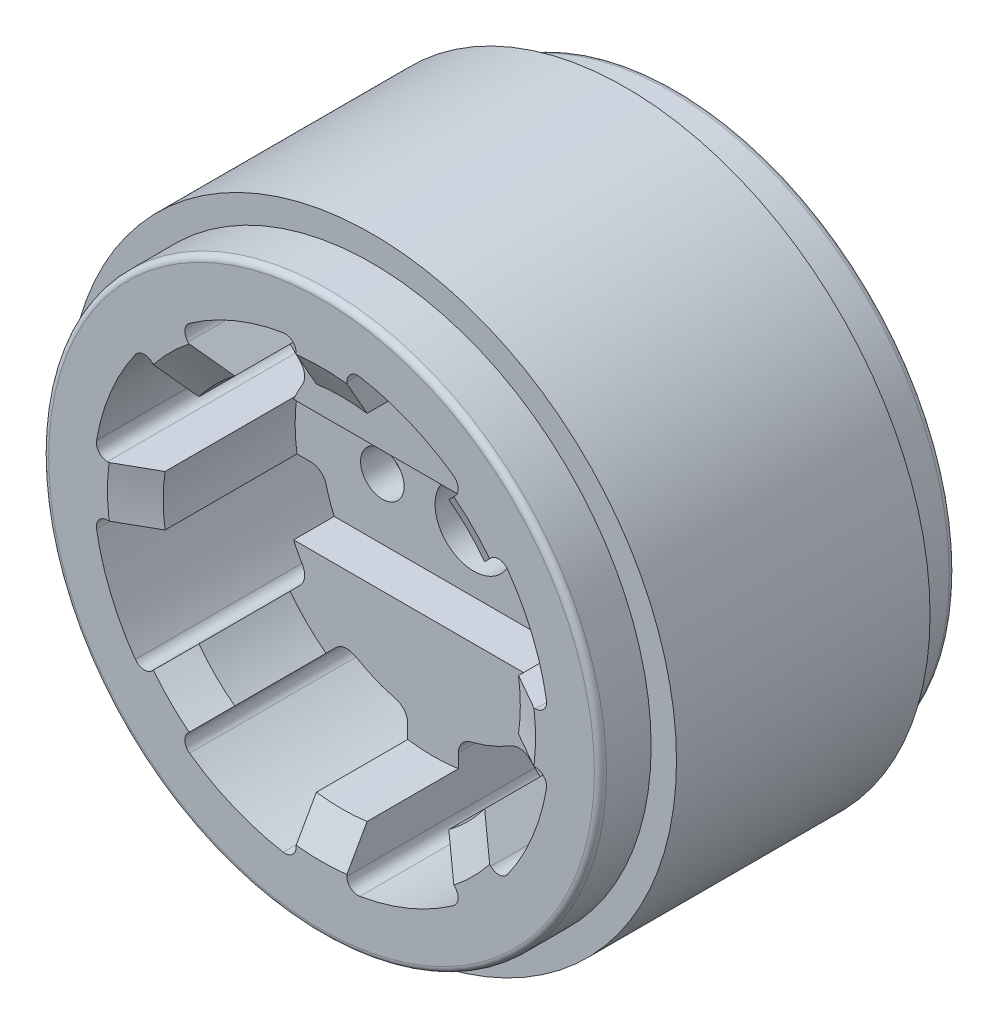
SolidWorks part; units mm, degrees
ref_plane "Front Plane" through (0, 0, 0) normal (0, 0, 1) x (1, 0, 0)
ref_plane "Top Plane" through (0, 0, 0) normal (0, 1, 0) x (1, 0, 0)
ref_plane "Right Plane" through (0, 0, 0) normal (1, 0, 0) x (0, 0, -1)
sketch "Sketch1" plane through (0, 0, 0) normal (0, 0, 1) x (1, 0, 0)
  line L0 (0, 0) -> (52.3745, 0) construction
  line L1 (0, 0) -> (0, 45.9782) construction
  line L2 (2.5, 21.1024) -> (2.5, 16.0565)
  line L3 (-13.7477, 6) -> (13.7477, 6)
  line L4 (-13.7477, -6) -> (13.7477, -6)
  line L5 (-2.5, 21.1024) -> (-2.5, 16.0565)
  line L6 (16.6894, 13.1539) -> (13.1215, 9.5859)
  line L7 (13.1539, 16.6894) -> (9.5859, 13.1215)
  line L8 (21.1024, -2.5) -> (16.0565, -2.5)
  line L9 (21.1024, 2.5) -> (16.0565, 2.5)
  line L10 (13.1539, -16.6894) -> (9.5859, -13.1215)
  line L11 (16.6894, -13.1539) -> (13.1215, -9.5859)
  line L12 (-2.5, -21.1024) -> (-2.5, -16.0565)
  line L13 (2.5, -21.1024) -> (2.5, -16.0565)
  line L14 (-16.6894, -13.1539) -> (-13.1215, -9.5859)
  line L15 (-13.1539, -16.6894) -> (-9.5859, -13.1215)
  line L16 (-21.1024, 2.5) -> (-16.0565, 2.5)
  line L17 (-21.1024, -2.5) -> (-16.0565, -2.5)
  line L18 (-13.1539, 16.6894) -> (-9.5859, 13.1215)
  line L19 (-16.6894, 13.1539) -> (-13.1215, 9.5859)
  circle A0 centre (0, 0) radius 3.8
  circle A1 centre (0, 0) radius 15
  circle A2 centre (0, 0) radius 22.5
  circle A3 centre (0, 0) radius 27.5
  circle A4 centre (9, 0) radius 3
  circle A5 centre (-9, 0) radius 3
  arc A6 (2.5, 21.1024) -> (3.7774, 22.1807) centre (3.5937, 21.1024) cw
  circle A7 centre (9, 0) radius 2.15
  circle A8 centre (-9, 0) radius 2.15
  arc A9 (-2.5, 21.1024) -> (-3.7774, 22.1807) centre (-3.5937, 21.1024) ccw
  arc A10 (16.6894, 13.1539) -> (18.3551, 13.0131) centre (17.4628, 12.3805) cw
  arc A11 (13.1539, 16.6894) -> (13.0131, 18.3551) centre (12.3805, 17.4628) ccw
  arc A12 (21.1024, -2.5) -> (22.1807, -3.7774) centre (21.1024, -3.5937) cw
  arc A13 (21.1024, 2.5) -> (22.1807, 3.7774) centre (21.1024, 3.5937) ccw
  arc A14 (13.1539, -16.6894) -> (13.0131, -18.3551) centre (12.3805, -17.4628) cw
  arc A15 (16.6894, -13.1539) -> (18.3551, -13.0131) centre (17.4628, -12.3805) ccw
  arc A16 (-2.5, -21.1024) -> (-3.7774, -22.1807) centre (-3.5937, -21.1024) cw
  arc A17 (2.5, -21.1024) -> (3.7774, -22.1807) centre (3.5937, -21.1024) ccw
  arc A18 (-16.6894, -13.1539) -> (-18.3551, -13.0131) centre (-17.4628, -12.3805) cw
  arc A19 (-13.1539, -16.6894) -> (-13.0131, -18.3551) centre (-12.3805, -17.4628) ccw
  arc A20 (-21.1024, 2.5) -> (-22.1807, 3.7774) centre (-21.1024, 3.5937) cw
  arc A21 (-21.1024, -2.5) -> (-22.1807, -3.7774) centre (-21.1024, -3.5937) ccw
  arc A22 (-13.1539, 16.6894) -> (-13.0131, 18.3551) centre (-12.3805, 17.4628) cw
  arc A23 (-16.6894, 13.1539) -> (-18.3551, 13.0131) centre (-17.4628, 12.3805) ccw
  circle A24 centre (0, 0) radius 30
  circle A25 centre (0, 0) radius 17.6
  circle A26 centre (0, 0) radius 21.25
  circle A27 centre (0, 0) radius 16.25
  arc A28 (2.5, 16.0565) -> (3.6792, 14.5418) centre (4.0625, 16.0565) ccw
  arc A29 (-2.5, 16.0565) -> (-3.6792, 14.5418) centre (-4.0625, 16.0565) cw
  arc A30 (13.1215, 9.5859) -> (12.8842, 7.681) centre (14.2263, 8.4811) ccw
  arc A31 (9.5859, 13.1215) -> (7.681, 12.8842) centre (8.4811, 14.2263) cw
  arc A32 (16.0565, -2.5) -> (14.5418, -3.6792) centre (16.0565, -4.0625) ccw
  arc A33 (16.0565, 2.5) -> (14.5418, 3.6792) centre (16.0565, 4.0625) cw
  arc A34 (9.5859, -13.1215) -> (7.681, -12.8842) centre (8.4811, -14.2263) ccw
  arc A35 (13.1215, -9.5859) -> (12.8842, -7.681) centre (14.2263, -8.4811) cw
  arc A36 (-2.5, -16.0565) -> (-3.6792, -14.5418) centre (-4.0625, -16.0565) ccw
  arc A37 (2.5, -16.0565) -> (3.6792, -14.5418) centre (4.0625, -16.0565) cw
  arc A38 (-13.1215, -9.5859) -> (-12.8842, -7.681) centre (-14.2263, -8.4811) ccw
  arc A39 (-9.5859, -13.1215) -> (-7.681, -12.8842) centre (-8.4811, -14.2263) cw
  arc A40 (-16.0565, 2.5) -> (-14.5418, 3.6792) centre (-16.0565, 4.0625) ccw
  arc A41 (-16.0565, -2.5) -> (-14.5418, -3.6792) centre (-16.0565, -4.0625) cw
  arc A42 (-9.5859, 13.1215) -> (-7.681, 12.8842) centre (-8.4811, 14.2263) ccw
  arc A43 (-13.1215, 9.5859) -> (-12.8842, 7.681) centre (-14.2263, 8.4811) cw
  point P87 (0, 0)
  point P138 (0, 0)
  dimension "D1" = 7.6
  dimension "D2" = 30
  dimension "D3" = 45
  dimension "D4" = 55
  dimension "D5" = 9
  dimension "D6" = 6
  dimension "D8" = 42.5
  dimension "D9" = 4.3
  dimension "D12" = 60
  dimension "D13" = 35.2
  dimension "D14" = 32.5
  dimension "D15" = 8
  dimension "D7" = 2.5
  dimension "D10" = 6
  dimension "D11" = 8
extrude "Boss-Extrude7" add sketch "Sketch1<15>" along normal blind 10 from offset 5 separate body contours A1
sketch "Sketch1<15>" plane through (0, 0, 0) normal (0, 0, 1) x (1, 0, 0) same geometry as "Sketch1"
extrude "Cut-Extrude2" cut sketch "Sketch1<16>" along normal blind 15 from surface contours A0 starting at face at (15, 0, 5)
sketch "Sketch1<16>" plane through (0, 0, 0) normal (0, 0, 1) x (1, 0, 0) same geometry as "Sketch1"
extrude "Cut-Extrude4" cut sketch "Sketch1<18>" along normal blind 7 from surface contours A5 | A4 starting at face at (3.8, 0, 5)
sketch "Sketch1<18>" plane through (0, 0, 0) normal (0, 0, 1) x (1, 0, 0) same geometry as "Sketch1"
extrude "Cut-Extrude5" cut sketch "Sketch1<19>" along normal blind 15 from surface contours A8 starting at face at (-6, 0, 5)
sketch "Sketch1<19>" plane through (0, 0, 0) normal (0, 0, 1) x (1, 0, 0) same geometry as "Sketch1"
extrude "Cut-Extrude6" cut sketch "Sketch1" along normal blind 15 from surface contours A7 starting at face at (-6, 0, 5)
extrude "Boss-Extrude12" add sketch "Sketch1<22>" along normal blind 4 from offset 15 contours L3 A1 | L4 A1 region at (0, 9.7124, 0) region at (0, -9.7124, 0)
sketch "Sketch1<22>" plane through (0, 0, 0) normal (0, 0, 1) x (1, 0, 0) same geometry as "Sketch1"
extrude "Boss-Extrude13" add sketch "Sketch1<23>" along normal blind 30 and the other way blind 5 separate body contours A3 A2 region at (-26.7222, 0, 0)
sketch "Sketch1<23>" plane through (0, 0, 0) normal (0, 0, 1) x (1, 0, 0) same geometry as "Sketch1"
extrude "Boss-Extrude14" add sketch "Sketch1<24>" along normal blind 25 and the other way blind 5 from offset 5 contours A26 A18 A2 A19 | A26 A20 A2 A21 | A26 A22 A2 A23 | A26 A6 A2 A9 | A26 A10 A2 A11 | A26 A12 A2 A13 | A26 A14 A2 A15 | A26 A16 A2 A17 region at (0, 21.849, 0) region at (15.4496, 15.4496, 0) region at (-15.4496, 15.4496, 0) region at (21.849, 0, 0) region at (-21.849, 0, 0) region at (15.4496, -15.4496, 0) region at (-15.4496, -15.4496, 0) region at (0, -21.849, 0)
sketch "Sketch1<24>" plane through (0, 0, 0) normal (0, 0, 1) x (1, 0, 0) same geometry as "Sketch1"
extrude "Boss-Extrude15" add sketch "Sketch1<25>" along normal blind 19 contours L18 A25 L19 A1 | L2 A25 L5 A1 | L6 A25 L7 A1 | L10 A25 L11 A1 | L12 A25 L13 A1 | L14 A25 L15 A1 | A27 A29 A1 A28 | A27 A31 A1 A30 | A27 A43 A1 A42 | A27 A35 A1 A34 | A27 A37 A1 A36 | A27 A39 A1 A38 region at (0, 16.863, 0) region at (0, 15.51, 0) region at (11.9239, 11.9239, 0) region at (10.9673, 10.9673, 0) region at (-11.9239, 11.9239, 0) region at (-10.9673, 10.9673, 0) region at (11.9239, -11.9239, 0) region at (-11.9239, -11.9239, 0) region at (10.9673, -10.9673, 0) region at (-10.9673, -10.9673, 0) region at (0, -16.863, 0) region at (0, -15.51, 0)
sketch "Sketch1<25>" plane through (0, 0, 0) normal (0, 0, 1) x (1, 0, 0) same geometry as "Sketch1"
extrude "Boss-Extrude16" add sketch "Sketch1<26>" along normal blind 10 and the other way blind 5 from offset 5 contours L8 A25 L9 A1 | L16 A25 L17 A1 | A27 A41 A1 A40 | A27 A33 A1 A32 region at (16.863, 0, 0) region at (15.51, 0, 0) region at (-16.863, 0, 0) region at (-15.51, 0, 0)
sketch "Sketch1<26>" plane through (0, 0, 0) normal (0, 0, 1) x (1, 0, 0) same geometry as "Sketch1"
extrude "Boss-Extrude18" add sketch "Sketch1<28>" along normal blind 25 contours A24 A3 region at (-29.1515, 0, 0)
sketch "Sketch1<28>" plane through (0, 0, 0) normal (0, 0, 1) x (1, 0, 0) same geometry as "Sketch1"
extrude "Boss-Extrude19" add sketch "Sketch1<32>" along normal blind 25 and the other way blind 5 from offset 5 contours L10 A26 L11 A25 | L8 A26 L9 A25 | L6 A26 L7 A25 | L2 A26 L5 A25 | L18 A26 L19 A25 | L16 A26 L17 A25 | L14 A26 L15 A25 | L12 A26 L13 A25 region at (0, 19.3706, 0) region at (13.6971, 13.6971, 0) region at (-13.6971, 13.6971, 0) region at (19.3706, 0, 0) region at (-19.3706, 0, 0) region at (13.6971, -13.6971, 0) region at (-13.6971, -13.6971, 0) region at (0, -19.3706, 0)
sketch "Sketch1<32>" plane through (0, 0, 0) normal (0, 0, 1) x (1, 0, 0) same geometry as "Sketch1"
chamfer "Chamfer2" distance 5 distance2 7.5 8 edges at (15, 0, 0) (10.6066, -10.6066, 0) (0, -15, 0) (-10.6066, -10.6066, 0) (-15, 0, 0) (-10.6066, 10.6066, 0) (0, 15, 0) (10.6066, 10.6066, 0) first distance on face at (14.7709, 0, 2.5) first distance on face at (10.4446, -10.4446, 2.5) first distance on face at (0, -14.7709, 2.5) first distance on face at (-10.4446, -10.4446, 2.5) first distance on face at (-14.7709, 0, 2.5) first distance on face at (-10.4446, 10.4446, 2.5) first distance on face at (0, 14.7709, 2.5) first distance on face at (10.4446, 10.4446, 2.5)
chamfer "Chamfer3" distance 3.5 distance2 2 8 edges at (17.6, 0, 30) (12.4451, -12.4451, 30) (0, -17.6, 30) (-12.4451, -12.4451, 30) (-17.6, 0, 30) (-12.4451, 12.4451, 30) (12.4451, 12.4451, 30) (0, 17.6, 30) first distance on face at (0, 0, 30)
fillet "Fillet1" radius 0.6 2 edges at (27.5, 0, -5) (27.5, 0, 30)
